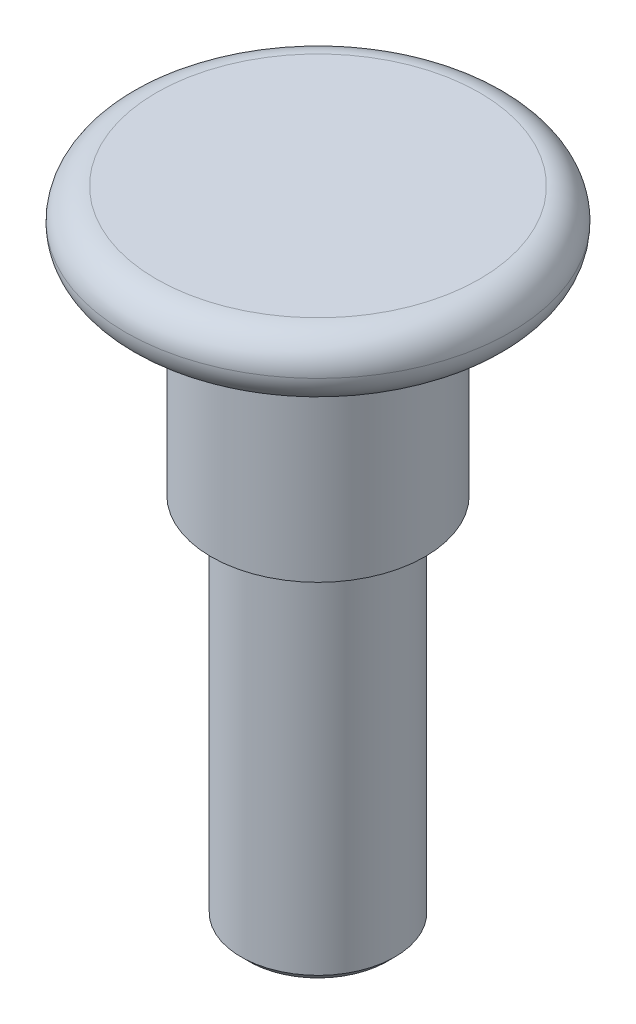
SolidWorks part; units mm, degrees
ref_plane "Plano frontal" through (0, 0, 0) normal (0, 0, 1) x (1, 0, 0)
ref_plane "Plano superior" through (0, 0, 0) normal (0, 1, 0) x (1, 0, 0)
ref_plane "Plano direito" through (0, 0, 0) normal (1, 0, 0) x (0, 0, -1)
sketch "Esboço1" plane through (0, 0, 0) normal (0, 0, 1) x (1, 0, 0)
  line L0 (0, -51.2852) -> (0, 57.5016) construction
  line L1 (0, 57.5016) -> (12.5, 57.5016)
  line L2 (12.5, 57.5016) -> (12.5, 53.5016)
  line L3 (12.5, 53.5016) -> (6.95, 53.5016)
  line L4 (6.95, 53.5016) -> (6.95, 40.1016)
  line L5 (6.95, 40.1016) -> (5, 40.1016)
  line L6 (5, 40.1016) -> (5, 16.1016)
  line L7 (5, 16.1016) -> (0, 16.1016)
  line L8 (0, 16.1016) -> (0, 57.5016)
  dimension "D1" = 12.5
  dimension "D2" = 6.95
  dimension "D3" = 5
  dimension "D4" = 4
  dimension "D5" = 13.4
  dimension "D6" = 24
revolve "Revolução1" add sketch "Esboço1" angle 360 about L0
fillet "Filete1" radius 2 2 edges at (0, 53.5016, -12.5) (0, 57.5016, -12.5)
chamfer "Chanfro1" distance 0.5 angle 45 1 edges at (0, 16.1016, -5)
